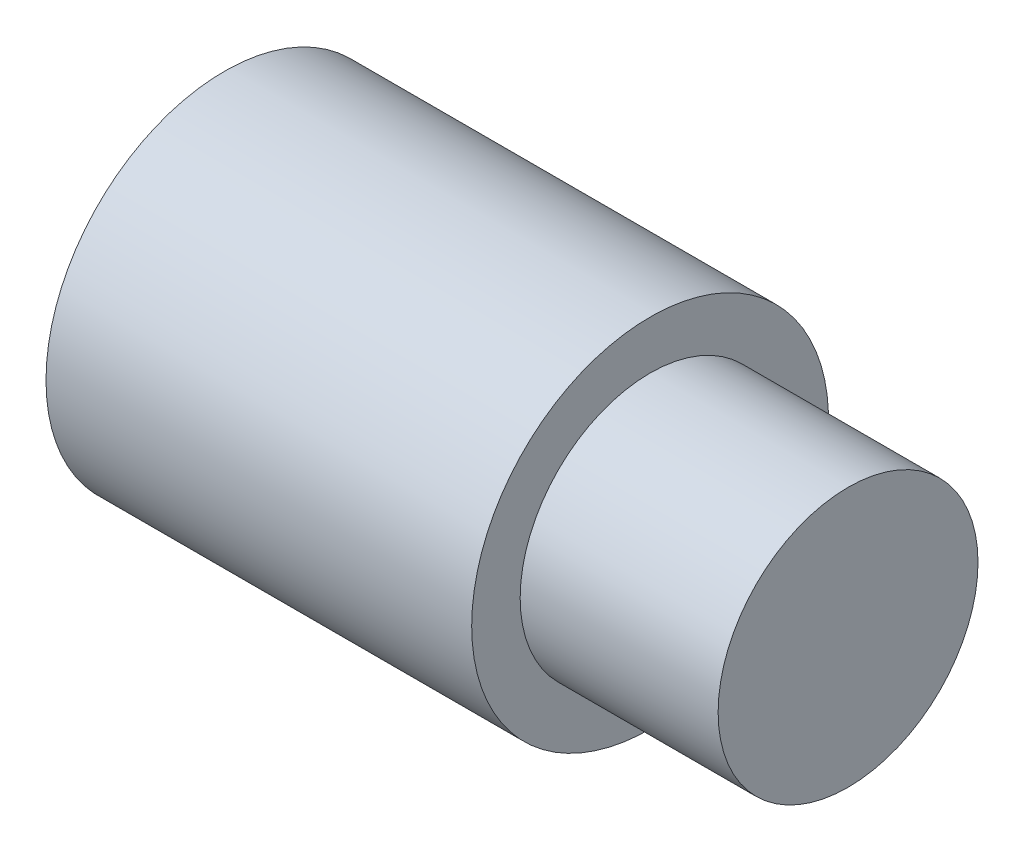
SolidWorks part; units mm, degrees
ref_plane "Front Plane" through (0, 0, 0) normal (0, 0, 1) x (1, 0, 0)
ref_plane "Top Plane" through (0, 0, 0) normal (0, 1, 0) x (1, 0, 0)
ref_plane "Right Plane" through (0, 0, 0) normal (1, 0, 0) x (0, 0, -1)
sketch "Conn_T8_ORB8 Sketch" plane through (0, 0, 0) normal (0, 0, 1) x (1, 0, 0)
  line L0 (-1000, 0) -> (1000, 0) construction
  line L1 (13.3, 0) -> (13.3, 8.73)
  line L2 (13.3, 8.73) -> (0, 8.73)
  line L3 (0, 8.73) -> (0, 11.988)
  line L4 (0, 11.988) -> (-28.6, 11.988)
  line L5 (-28.6, 11.988) -> (-28.6, 0)
  line L6 (-28.6, 0) -> (13.3, 0)
revolve "Conn_T8_ORB8" add sketch "Conn_T8_ORB8 Sketch" angle 360 about L0
ref_axis "Engine Axis" through (15.395, 0, 0) along (-1, 0, 0)
sketch "Socket Sketch" plane through (0, 0, 0) normal (0, 0, 1) x (1, 0, 0)
  line L0 (-1000, 0) -> (1000, 0) construction
  line L1 (-29.6, 0) -> (-29.6, 6.35)
  line L2 (-29.6, 6.35) -> (-5.7, 6.35)
  line L3 (-5.7, 6.35) -> (-5.7, 0)
  line L4 (-5.7, 0) -> (-29.6, 0)
revolve "Socket" cut sketch "Socket Sketch" angle 360 about L0
